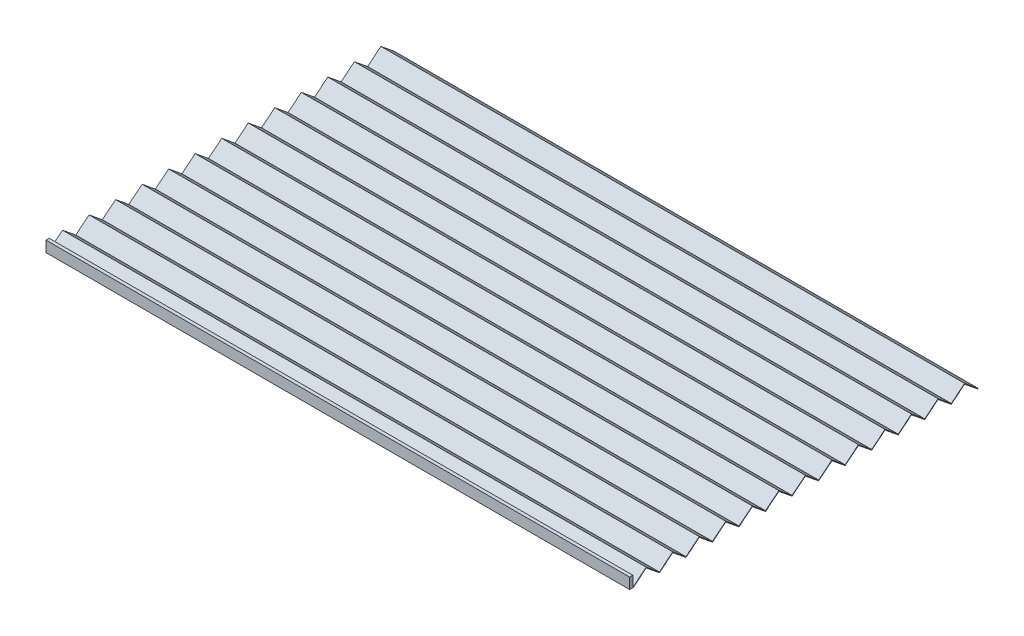
SolidWorks part; units mm, degrees
ref_plane "Front Plane" through (0, 0, 0) normal (0, 0, 1) x (1, 0, 0)
ref_plane "Top Plane" through (0, 0, 0) normal (0, 1, 0) x (1, 0, 0)
ref_plane "Right Plane" through (0, 0, 0) normal (1, 0, 0) x (0, 0, -1)
sketch "Sketch2" plane through (0, 0, 0) normal (0, 0, 1) x (1, 0, 0)
  line L1 (-270, 10) -> (270, 10)
  line L2 (-270, 10) -> (-270, 0)
  line L3 (-270, 0) -> (270, 0)
  line L4 (270, 10) -> (270, 0)
  point P4 (0, 0)
  dimension "D1" = 10
  dimension "D2" = 540
extrude "Boss-Extrude1" add sketch "Sketch2" along normal blind 3
sketch "Sketch3" plane through (270, 0, 0) normal (1, 0, 0) x (0, 0, -1)
  line L0 (0, 10) -> (319.0954, 10) construction
  line L1 (0, 0) -> (319.0954, 0) construction
  line L2 (319.0954, 10) -> (319.0954, 0) construction
  line L3 (0, 0) -> (12.2729, 10)
  line L4 (12.2729, 10) -> (24.5458, 0)
  line L5 (24.5458, 0) -> (36.8187, 10)
  line L6 (36.8187, 10) -> (49.0916, 0)
  line L7 (49.0916, 0) -> (61.3645, 10)
  line L8 (61.3645, 10) -> (73.6374, 0)
  line L9 (73.6374, 0) -> (85.9103, 10)
  line L10 (85.9103, 10) -> (98.1832, 0)
  line L11 (98.1832, 0) -> (110.4561, 10)
  line L12 (110.4561, 10) -> (122.729, 0)
  line L13 (122.729, 0) -> (135.0019, 10)
  line L14 (135.0019, 10) -> (147.2748, 0)
  line L15 (147.2748, 0) -> (159.5477, 10)
  line L16 (159.5477, 10) -> (171.8206, 0)
  line L17 (171.8206, 0) -> (184.0935, 10)
  line L18 (184.0935, 10) -> (196.3664, 0)
  line L20 (196.3664, 0) -> (208.6393, 10)
  line L21 (208.6393, 10) -> (220.9122, 0)
  line L22 (220.9122, 0) -> (233.1851, 10)
  line L23 (233.1851, 10) -> (245.458, 0)
  line L24 (245.458, 0) -> (257.7309, 10)
  line L25 (257.7309, 10) -> (270.0038, 0)
  line L26 (270.0038, 0) -> (282.2767, 10)
  line L27 (282.2767, 10) -> (294.5496, 0)
  line L28 (294.5496, 0) -> (306.8225, 10)
  line L29 (306.8225, 10) -> (319.0954, 0)
  line L30 (319.0954, 10) -> (319.0954, 0) construction
extrude "Extrude-Thin1" add sketch "Sketch3" against normal through all thin thin type mid plane wall 0.5
